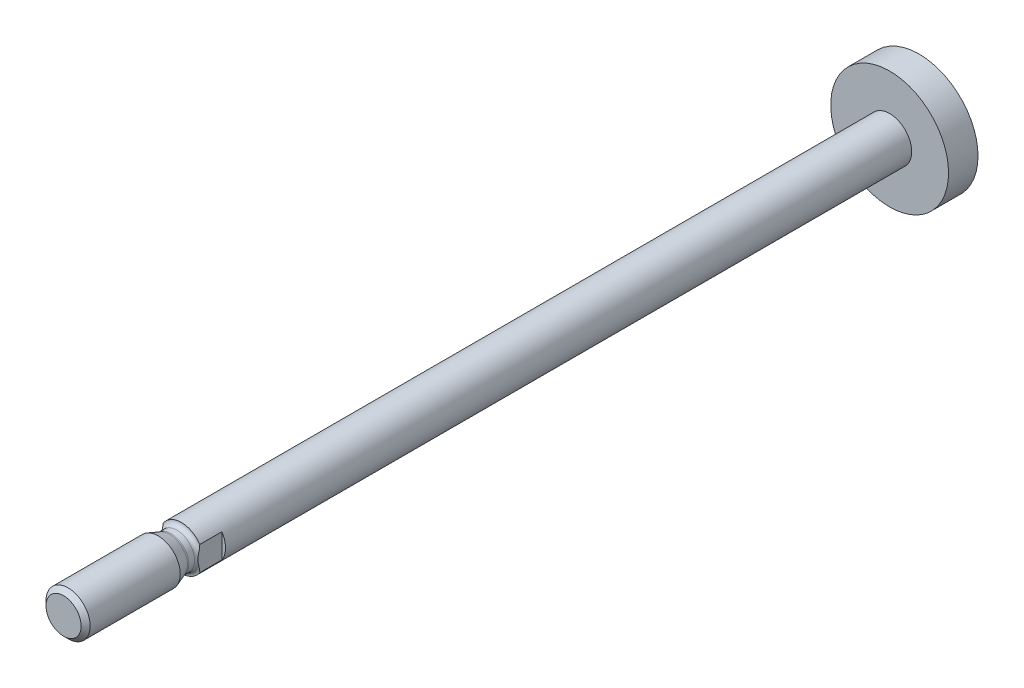
SolidWorks part; units mm, degrees
ref_plane "Front Plane" through (0, 0, 0) normal (0, 0, 1) x (1, 0, 0)
ref_plane "Top Plane" through (0, 0, 0) normal (0, 1, 0) x (1, 0, 0)
ref_plane "Right Plane" through (0, 0, 0) normal (1, 0, 0) x (0, 0, -1)
sketch "Sketch1" plane through (0, 0, 0) normal (1, 0, 0) x (0, 0, -1)
  line L0 (-5, 0) -> (-5, 3)
  line L1 (-5, 3) -> (91.2, 3)
  line L2 (91.2, 3) -> (91.2, 8)
  line L3 (91.2, 8) -> (95.2, 8)
  line L4 (95.2, 8) -> (95.2, 0)
  line L5 (95.2, 0) -> (-5, 0)
  line L6 (95.2, 0) -> (-5, 0) construction
revolve "Revolve1" add sketch "Sketch1" angle 360 about L6 reverse direction yes
sketch "Sketch2" plane through (0, 0, 0) normal (1, 0, 0) x (0, 0, -1)
  line L0 (-21, 0) -> (-21, 2.3865)
  line L1 (-21, 2.3865) -> (-20.3865, 3)
  line L2 (-20.3865, 3) -> (-8.1485, 3)
  line L3 (-8.1485, 3) -> (-6.5994, 2.4362)
  line L4 (-6.3942, 2.4) -> (-5.6, 2.4)
  line L5 (-5, 3) -> (-4, 3)
  line L6 (-4, 3) -> (-4, 0)
  line L7 (-4, 0) -> (-21, 0)
  line L8 (-4, 0) -> (-21, 0) construction
  arc A0 (-6.5994, 2.4362) -> (-6.3942, 2.4) centre (-6.3942, 3) ccw
  arc A1 (-5.6, 2.4) -> (-5, 3) centre (-5.6, 3) ccw
revolve "Revolve2" add sketch "Sketch2" angle 360 about L8 reverse direction yes
cosmetic thread "Cosmetic Thread1" parameters "D1"=12.8515, "D2"=4.773
ref_plane "Plane1" through (0, 0, 5) normal (0, 0, 1) x (1, 0, 0)
ref_plane "Plane2" through (0, 0, 2) normal (0, 0, 1) x (1, 0, 0)
sketch "Sketch3" plane through (0, 0, 2) normal (0, 0, 1) x (1, 0, 0)
  line L0 (-5, 10) -> (-5, -5)
  line L1 (-5, -5) -> (-2.5, -5)
  line L2 (-2.5, -5) -> (-2.5, 5)
  line L3 (-2.5, 5) -> (2.5, 5)
  line L4 (2.5, 5) -> (2.5, -5)
  line L5 (2.5, -5) -> (5, -5)
  line L6 (5, -5) -> (5, 10)
  line L7 (5, 10) -> (-5, 10)
extrude "Cut-Extrude1" cut sketch "Sketch3" along normal blind 4
ref_plane "Plane3" through (0, 0, -195) normal (0, 0, 1) x (1, 0, 0)
ref_plane "Plane4" through (0, 0, 16) normal (0, 0, 1) x (1, 0, 0)
ref_plane "Plane5" through (0, 0, 11.2) normal (0, 0, 1) x (1, 0, 0)
ref_plane "FDT_KSAUFSATZ XY" through (0, 0, 11.2) normal (0, 0, 1) x (1, 0, 0)
ref_plane "FDT_KSAUFSATZ XZ" through (0, 0, 0) normal (0, 1, 0) x (1, 0, 0)
ref_plane "FDT_KSAUFSATZ YZ" through (0, 0, 0) normal (-1, 0, 0) x (0, 0, 1)
ref_axis "FDT_KSAUFSATZ X" through (80.9, 0, 11.2) along (-1, 0, 0)
ref_axis "FDT_KSAUFSATZ Y" through (0, 50, 11.2) along (0, -1, 0)
ref_axis "FDT_KSAUFSATZ Z" through (0, 0, 80.9) along (0, 0, -1)
sketch3d "FDT_KSAUFSATZ"
  point P0 (0, 0, 11.2)
ref_plane "FDT_NUT XY" through (0, 0, 11.2) normal (0, 0, 1) x (1, 0, 0)
ref_plane "FDT_NUT XZ" through (0, 0, 0) normal (0, 1, 0) x (1, 0, 0)
ref_plane "FDT_NUT YZ" through (0, 0, 0) normal (-1, 0, 0) x (0, 0, 1)
ref_axis "FDT_NUT X" through (80.9, 0, 11.2) along (-1, 0, 0)
ref_axis "FDT_NUT Y" through (0, 50, 11.2) along (0, -1, 0)
ref_axis "FDT_NUT Z" through (0, 0, 80.9) along (0, 0, -1)
sketch3d "FDT_NUT"
  point P0 (0, 0, 11.2)
ref_plane "KS XY" through (0, 0, 0) normal (0, 0, -1) x (-1, 0, 0)
ref_plane "KS XZ" through (0, 0, 0) normal (0, 1, 0) x (1, 0, 0)
ref_plane "KS YZ" through (0, 0, 0) normal (1, 0, 0) x (0, 0, -1)
ref_axis "KS X" through (-80.9, 0, 0) along (1, 0, 0)
ref_axis "KS Y" through (0, 50, 0) along (0, -1, 0)
ref_axis "KS Z" through (0, 0, -80.9) along (0, 0, 1)
sketch3d "KS"
  point P0 (0, 0, 0)
ref_plane "NUT1 XY" through (0, 0, 16) normal (0, 0, 1) x (1, 0, 0)
ref_plane "NUT1 XZ" through (0, 0, 0) normal (0, -1, 0) x (-1, 0, 0)
ref_plane "NUT1 YZ" through (0, 0, 0) normal (1, 0, 0) x (0, 0, -1)
ref_axis "NUT1 X" through (-80.9, 0, 16) along (1, 0, 0)
ref_axis "NUT1 Y" through (0, -50, 16) along (0, 1, 0)
ref_axis "NUT1 Z" through (0, 0, 80.9) along (0, 0, -1)
sketch3d "NUT1"
  point P0 (0, 0, 16)
